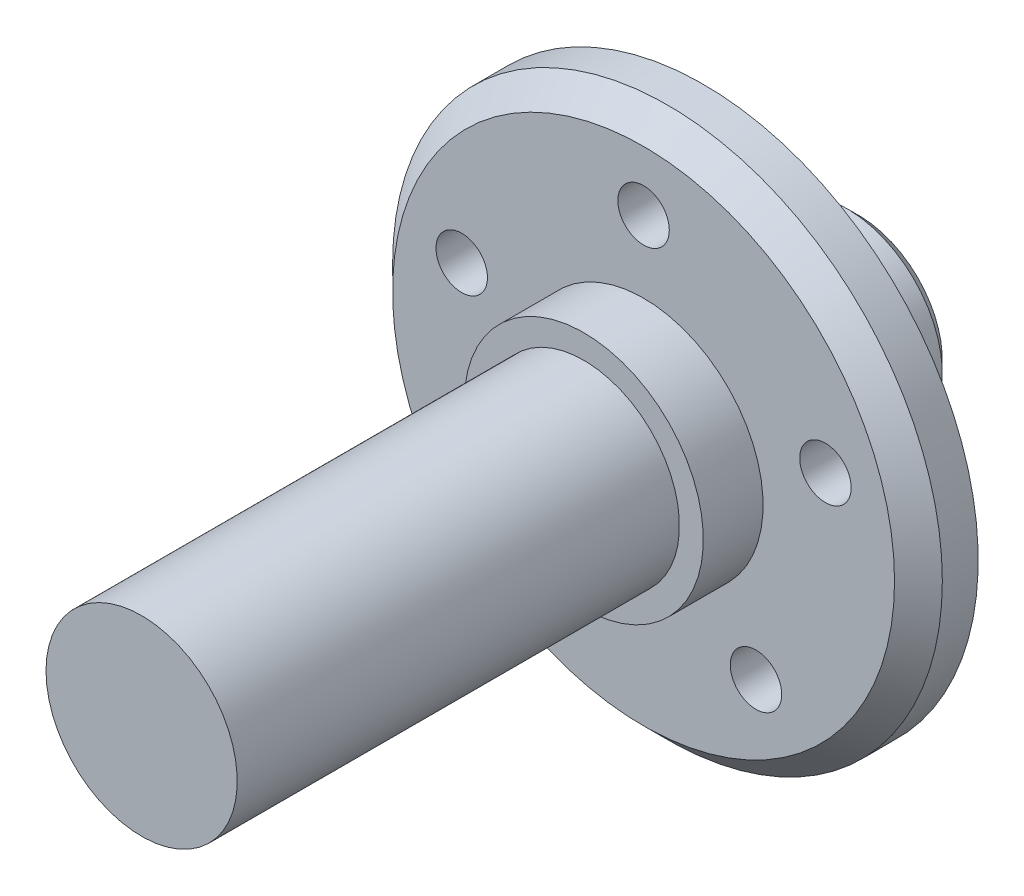
SolidWorks part; units mm, degrees
ref_plane "Front Plane" through (0, 0, 0) normal (0, 0, 1) x (1, 0, 0)
ref_plane "Top Plane" through (0, 0, 0) normal (0, 1, 0) x (1, 0, 0)
ref_plane "Right Plane" through (0, 0, 0) normal (1, 0, 0) x (0, 0, -1)
sketch "Sketch3" plane through (0, 0, 0) normal (0, 1, 0) x (1, 0, 0)
  line L0 (0, 0) -> (-8, 0)
  line L1 (-8, 0) -> (-8, 37)
  line L2 (-8, 37) -> (-10, 37)
  line L5 (0, 60) -> (0, 0)
  line L6 (-10, 37) -> (-10, 42)
  line L7 (-10, 42) -> (-23, 42)
  line L8 (-23, 42) -> (-23, 47)
  line L9 (-23, 47) -> (-8, 47)
  line L10 (-8, 47) -> (-8, 60)
  line L11 (-8, 60) -> (0, 60)
  dimension "D1" = 60
  dimension "D3" = 8
  dimension "D2" = 10
  dimension "D5" = 5
  dimension "D6" = 5
  dimension "D4" = 23
  dimension "D7" = 8
  dimension "D8" = 13
revolve "Revolve1" add sketch "Sketch3" angle 360 about L5
chamfer "Chamfer1" distance 2 angle 45 1 edges at (-23, 0, -42)
sketch "Placement Sketch" plane through (0, 0, -42) normal (0, 0, 1) x (1, 0, 0)
  line L0 (0, 0) -> (0, 16) construction
  point P0 (0, 16)
  point P1 (15.2169, 4.9443)
  point P5 (9.4046, -12.9443)
  point P6 (-9.4046, -12.9443)
  point P7 (-15.2169, 4.9443)
  dimension "D1" = 16
  dimension "D2" = 5
hole_wizard "#8 Clearance Hole1" positions "Placement Sketch" profile "Sketch5" hole size "#8" standard "ANSI Inch"
sketch "Sketch5" plane through (0, 16, -42) normal (1, 0, 0) x (0, -1, 0)
  line L0 (0, 0) -> (0, 13.2934)
  line L1 (0, 13.2934) -> (2.1526, 12)
  line L2 (2.1526, 12) -> (2.1526, 0)
  line L5 (2.1526, 0) -> (0, 0)
  line L10 (0, 13.2934) -> (-2.1527, 12) construction
  line L11 (0, -6.35) -> (0, 107.95) construction
  dimension "Hole Dia." = 4.3053
  dimension "Hole Depth" = 12
  dimension "Drill Angle" = 118
chamfer "Chamfer2" distance 1 angle 45 1 edges at (-8, 0, -60)
equation "\"thin_diameter\"= 16"
equation "\"thick_diameter\"= 20"
equation "\"D3@Sketch3\" = \"thin_diameter\" / 2"
equation "\"D2@Sketch3\" = \"thick_diameter\" / 2"
equation "\"flange_diameter\"= 46"
equation "\"flange_thickness\"= 5"
equation "\"D5@Sketch3\"=\"flange_thickness\""
equation "\"D4@Sketch3\"=\"flange_diameter\" / 2"
equation "\"back_diameter\"= 16"
equation "\"D7@Sketch3\"=\"back_diameter\" / 2"
equation "\"turbine_thickness\"= 13"
equation "\"D8@Sketch3\"=\"turbine_thickness\""
